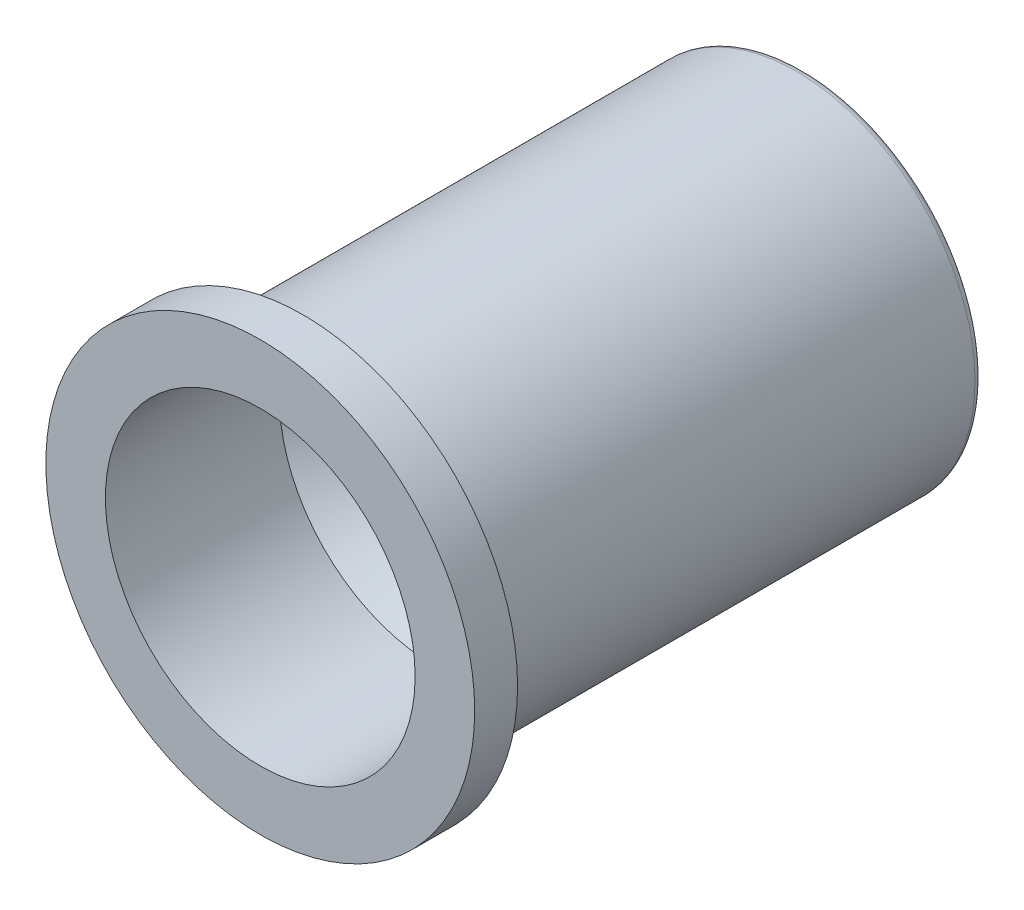
SolidWorks part; units mm, degrees
ref_plane "Front" through (0, 0, 0) normal (0, 0, 1) x (1, 0, 0)
ref_plane "Top" through (0, 0, 0) normal (0, 1, 0) x (1, 0, 0)
ref_plane "Right" through (0, 0, 0) normal (1, 0, 0) x (0, 0, -1)
sketch "Sketch3" plane through (0, 0, 0) normal (0, 0, 1) x (1, 0, 0)
  circle A0 centre (0, 0) radius 9
  dimension "dk" = 18
extrude "BaseHead" add sketch "Sketch3" against normal blind 1.8
sketch "Sketch4" plane through (-1.8728, 0.3563, -1.8) normal (0, 0, -1) x (-1, 0, 0)
  circle A0 centre (-1.8728, -0.3563) radius 7.5
  circle A1 centre (-1.8728, -0.3563) radius 9 construction
  dimension "d" = 15
extrude "BaseBody" add sketch "Sketch4" along normal blind 21
sketch "Sketch5" plane through (-1.3755, 3.4749, 0) normal (0, 0, 1) x (1, 0, 0)
  circle A0 centre (1.3755, -3.4749) radius 6.5
  circle A1 centre (1.3755, -3.4749) radius 9 construction
extrude "Hole1" cut sketch "Sketch5" against normal blind 7.3
sketch "Sketch6" plane through (0.0322, 0.3953, -7.3) normal (0, 0, 1) x (1, 0, 0)
  circle A0 centre (-0.0322, -0.3953) radius 5
  circle A1 centre (-0.0322, -0.3953) radius 6.5 construction
  dimension "D1" = 10
extrude "Hole2" cut sketch "Sketch6" against normal through all
cosmetic thread "ThreadCosmetic1" [suppressed] parameters "D2"=12
fillet "Fillet1" radius 0.3 2 edges at (-7.5, 0, -22.8) (7.5, 0, -1.8)
chamfer "Chamfer1" distance 1.5 angle 45 1 edges at (5, 0, -7.3)
chamfer "Chamfer2" distance 0.5 angle 45 1 edges at (5, 0, -22.8)
sketch "Sketch7" plane through (0, 0, 0) normal (1, 0, 0) x (0, 0, -1)
  line L0 (28.4249, 0) -> (15.7466, 0) construction
  line L1 (21.8, -4) -> (22.8, -4)
  line L2 (22.8, -4) -> (22.8, -5)
  line L3 (22.8, -5) -> (22.3, -5.866)
  line L4 (22.3, -5.866) -> (21.8, -5)
  line L5 (21.8, -5) -> (21.8, -4)
  line L6 (22.3, 5) -> (22.3, -5) construction
  dimension "D1" = 10
revolve "Cut-Revolve10" [suppressed] cut sketch "Sketch7" angle 360 about L0
pattern_linear "LPattern10" [suppressed] count 12 spacing 1.2 along (0, 0, 1) of bodies 105
equation "\"D1@Chamfer1\" = (  \"d1@Sketch5\" - \"D1@Sketch6\" )  / 2"
equation "\"D1@Chamfer2\" = \"D1@Sketch6\" / 20"
equation "\"D1@Sketch7\" = \"D1@Sketch6\""
equation "\"D2@Sketch7\" = (  \"D2@ThreadCosmetic1\" - \"D1@Sketch6\" )  / 2"
equation "\"D3@LPattern10\" = \"D2@Sketch7\" * 1.2"
equation "\"D1@LPattern10\" =  ( \"l@BaseBody\" + \"k@BaseHead\"  - \"l1@Hole1\")  / \"D3@LPattern10\" - 1"
